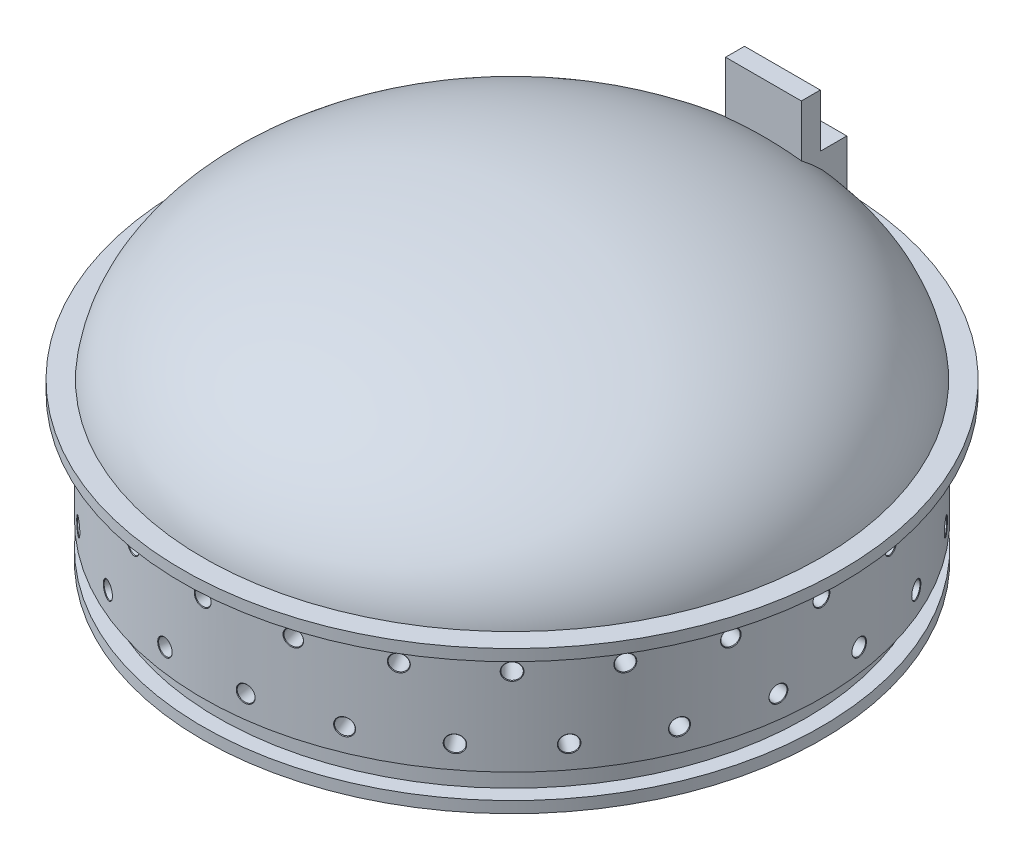
SolidWorks part; units mm, degrees
material "AW-6082-T6 (PA4)"
ref_plane "Płaszczyzna przednia" through (0, 0, 0) normal (0, 0, 1) x (1, 0, 0)
ref_plane "Płaszczyzna górna" through (0, 0, 0) normal (0, 1, 0) x (1, 0, 0)
ref_plane "Płaszczyzna prawa" through (0, 0, 0) normal (1, 0, 0) x (0, 0, -1)
sketch "Szkic1" plane through (0, 0, 0) normal (0, 1, 0) x (1, 0, 0)
  circle A0 centre (0, 0) radius 81.7
  dimension "D1" = 163.4
extrude "Dodanie-wyciągnięcie1" add sketch "Szkic1" along normal blind 38.5
ref_plane "Płaszczyzna1" through (0, 0, -81.7) normal (0, 0, -1) x (-1, 0, 0)
ref_plane "Płaszczyzna2" through (10.664, 0, -81.001) normal (0.1305, 0, -0.9914) x (0, -1, 0)
hole_wizard "Otwór gwintowany M51" positions "Szkic2" profile "Szkic3" hole size "M5" standard "ISO"
sketch "Szkic2" plane through (0, 0, -81.7) normal (0, 0, -1) x (-1, 0, 0)
  line L0 (81.7, 0) -> (81.7, 38.5) construction
  line L1 (-81.7, 38.5) -> (-81.7, 0) construction
  line L2 (81.7, 0) -> (81.7, 38.5)
  line L3 (-81.7, 38.5) -> (-81.7, 0)
  line L4 (0, 51.4702) -> (0, -13.4001) construction
  line L5 (81.7, 38.5) -> (-81.7, 38.5) construction
  point P11 (0, 32.5)
  dimension "D1" = 6
sketch "Szkic3" plane through (0, 32.5, -81.7) normal (1, 0, 0) x (0, 1, 0)
  line L0 (0, 0) -> (0, 9.2618)
  line L1 (0, 9.2618) -> (2.1, 8)
  line L2 (2.1, 8) -> (2.1, 0.15)
  line L3 (2.1, 0.15) -> (2.25, 0)
  line L5 (2.25, 0) -> (0, 0)
  line L6 (-2.1, 0.15) -> (-2.25, 0) construction
  line L10 (0, 9.2618) -> (-2.1, 8) construction
  line L11 (0, -6.35) -> (0, 107.95) construction
  dimension "Średnica otworu" = 4.2
  dimension "Głębokośc otworu" = 8
  dimension "Średnica zewnętrznego pogłębienia stożkowego" = 4.5
  dimension "Kąt zewnętrznego pogłębienia stożkowego" = 90
  dimension "Kąt wiertła" = 118
hole_wizard "Otwór gwintowany M52" positions "Szkic6" profile "Szkic7" hole size "M5" standard "ISO"
sketch "Szkic6" plane through (10.664, 0, -81.001) normal (0.1305, 0, -0.9914) x (0, -1, 0)
  line L0 (-38.5, -81.7) -> (0, -81.7) construction
  line L1 (0, 81.7) -> (-38.5, 81.7) construction
  line L2 (-38.5, -81.7) -> (0, -81.7)
  line L3 (0, 81.7) -> (-38.5, 81.7)
  line L4 (-54.6249, 0) -> (16.9218, 0) construction
  ellipse E0 centre (-32.5, 10.6444) end of major axis (-30.4, 10.6444) minor radius 2.082 construction
  point P10 (-15.5, 0)
  dimension "D1" = 17
sketch "Szkic7" plane through (10.664, 15.5, -81.001) normal (0, 1, 0) x (-0.9914, 0, -0.1305)
  line L0 (0, 0) -> (0, 9.2618)
  line L1 (0, 9.2618) -> (2.1, 8)
  line L2 (2.1, 8) -> (2.1, 0.15)
  line L3 (2.1, 0.15) -> (2.25, 0)
  line L5 (2.25, 0) -> (0, 0)
  line L6 (-2.1, 0.15) -> (-2.25, 0) construction
  line L10 (0, 9.2618) -> (-2.1, 8) construction
  line L11 (0, -6.35) -> (0, 107.95) construction
  dimension "Średnica otworu" = 4.2
  dimension "Głębokośc otworu" = 8
  dimension "Średnica zewnętrznego pogłębienia stożkowego" = 4.5
  dimension "Kąt zewnętrznego pogłębienia stożkowego" = 90
  dimension "Kąt wiertła" = 118
pattern_circular "Szyk kołowy1" count 24 over 360 about axis through (0, 38.5, 0) along (0, -1, 0) of "Otwór gwintowany M51", "Otwór gwintowany M52"
sketch "Szkic8" plane through (0, 0, 0) normal (0, 0, 1) x (1, 0, 0)
  line L0 (-81.7, 30.25) -> (-81.7, 0) construction
  line L1 (-81.7, 30.25) -> (-81.7, 0)
  line L2 (-81.7, 0) -> (81.7, 0) construction
  line L3 (-81.7, 9.5) -> (-77.7, 9.5)
  line L4 (-81.7, 9.5) -> (-81.7, 3)
  line L5 (-81.7, 3) -> (-77.7, 3)
  line L6 (-77.7, 9.5) -> (-77.7, 3)
  line L8 (0, 56.0732) -> (0, -20.5484) construction
  line L9 (81.7, 0) -> (81.7, 30.25) construction
  dimension "D1" = 4
  dimension "D2" = 6.5
  dimension "D3" = 3
revolve "Wycięcie-obrót1" cut sketch "Szkic8" angle 360 about L8 region at (-79.7, 6.25, 0)
sketch "Szkic9" plane through (0, 0, 0) normal (0, 0, 1) x (1, 0, 0)
  line L0 (0, -10.2266) -> (0, 51.1756) construction
  line L1 (-81.7, 0) -> (81.7, 0) construction
  line L2 (0, 0) -> (-66.7, 0)
  line L3 (0, 0) -> (0, 23.5)
  line L4 (0, 23.5) -> (-66.7, 23.5)
  line L5 (-66.7, 0) -> (-66.7, 23.5)
  line L6 (-81.7, 30.2501) -> (-81.7, 9.5) construction
  line L7 (-81.7, 30.2501) -> (-81.7, 9.5)
  line L8 (-73.7, 34.6) -> (-73.7, 30.4) construction
  line L9 (81.7, 38.5) -> (-81.7, 38.5) construction
  line L10 (81.7, 38.5) -> (-81.7, 38.5)
  dimension "D1" = 15
  dimension "D2" = 7
  dimension "D3" = 15
revolve "Wycięcie-obrót2" cut sketch "Szkic9" angle 360 about L0 region at (-33.35, 11.75, 0)
sketch "Szkic10" plane through (0, 23.5, 0) normal (0, -1, 0) x (1, 0, 0)
  circle A1 centre (0, 0) radius 66.7
  circle A2 centre (0, 0) radius 66.7
  dimension "D1" = 0
extrude "Wytnij-wyciągnięcie1" cut sketch "Szkic10" against normal through all
sketch "Szkic11" plane through (0, 0, 0) normal (0, 0, 1) x (1, 0, 0)
  line L0 (0, 38.5) -> (0, 98.1331) construction
  line L1 (66.7, 38.5) -> (-66.7, 38.5) construction
  line L2 (0, 38.5) -> (-66.7, 38.5) construction
  line L4 (66.7, 38.5) -> (81.7, 38.5)
  line L5 (0, 82) -> (0, 71)
  ellipse E0 centre (0, 38.5) end of major axis (66.7, 38.5) minor radius 32.5 (66.7, 38.5) -> (0, 71) ccw
  ellipse E1 centre (0, 38.5) end of major axis (-81.7, 38.5) minor radius 43.5 (81.7, 38.5) -> (0, 82) ccw
  dimension "D1" = 43.5
  dimension "D2" = 11
revolve "Obrót3" add sketch "Szkic11" angle 360 about L0
chamfer "Sfazowanie1" distance 9 angle 45 1 edges at (0, 0, -66.7)
sketch "Szkic12" plane through (0, 0, 0) normal (0, 0, 1) x (1, 0, 0)
  line L0 (66.7, 38.5) -> (-66.7, 38.5) construction
  line L1 (66.7, 38.5) -> (-66.7, 38.5) construction
  line L2 (0, 38.5) -> (0, 97.1164) construction
  line L4 (-76.7, 38.5) -> (-87, 38.5)
  line L5 (-76.7, 38.5) -> (-76.7, 41.5)
  line L6 (-76.7, 41.5) -> (-87, 41.5)
  line L7 (-87, 38.5) -> (-87, 41.5)
  point P9 (-76.7, 40)
  dimension "D1" = 3
  dimension "D2" = 87
  dimension "D3" = 10
revolve "Obrót4" add sketch "Szkic12" angle 360 about L2
ref_point "Punkt1"
ref_plane "Płaszczyzna3" through (0, 82, 0) normal (0, 1, 0) x (1, 0, 0)
sketch "Szkic13" plane through (0, 82, 0) normal (0, 1, 0) x (1, 0, 0)
  line L0 (0, 0) -> (0, 87) construction
  line L2 (-10, 66.3645) -> (10, 66.3645)
  line L3 (-10, 66.3645) -> (-10, 71.3645)
  line L4 (-10, 71.3645) -> (10, 71.3645)
  line L5 (10, 66.3645) -> (10, 71.3645)
  line L6 (-10, 66.3645) -> (10, 71.3645) construction
  line L7 (-10, 71.3645) -> (10, 66.3645) construction
  line L8 (-10, 71.3645) -> (10, 71.3645) construction
  line L9 (-10, 71.3645) -> (-10, 78.3645) construction
  line L10 (-10, 78.3645) -> (10, 78.3645) construction
  line L11 (10, 71.3645) -> (10, 78.3645) construction
  circle A0 centre (0, 0) radius 87 construction
  circle A1 centre (0, 0) radius 87 construction
  circle A2 centre (0, 0) radius 72.0618 construction
  circle A3 centre (0, 0) radius 79 construction
  point P4 (0, 68.8645)
  dimension "D1" = 7
  dimension "D4" = 8
  dimension "D2" = 5
  dimension "D3" = 20
extrude "Dodanie-wyciągnięcie2" add sketch "Szkic13" against normal up to surface (13.6938 mm away) from offset 5 offset against normal yes
ref_plane "Płaszczyzna4" through (0, 63, 0) normal (0, 1, 0) x (1, 0, 0)
sketch "Szkic14" plane through (0, 63, 0) normal (0, 1, 0) x (1, 0, 0)
  line L0 (10, 71.3645) -> (-10, 71.3645) construction
  line L1 (10, 71.3645) -> (-10, 71.3645)
  line L3 (-10, 71.3645) -> (10, 71.3645)
  line L4 (-10, 71.3645) -> (-10, 78.3645)
  line L5 (-10, 78.3645) -> (10, 78.3645)
  line L6 (10, 71.3645) -> (10, 78.3645)
  dimension "D1" = 7
extrude "Dodanie-wyciągnięcie3" add sketch "Szkic14" against normal up to surface (4.003 mm away) contours L1 L6 L5 L4 region at (0, 63, -74.8645) up to face at (0, 61.1516, -68.8645)
equation "\"D2@Szkic12\"=174/2"
